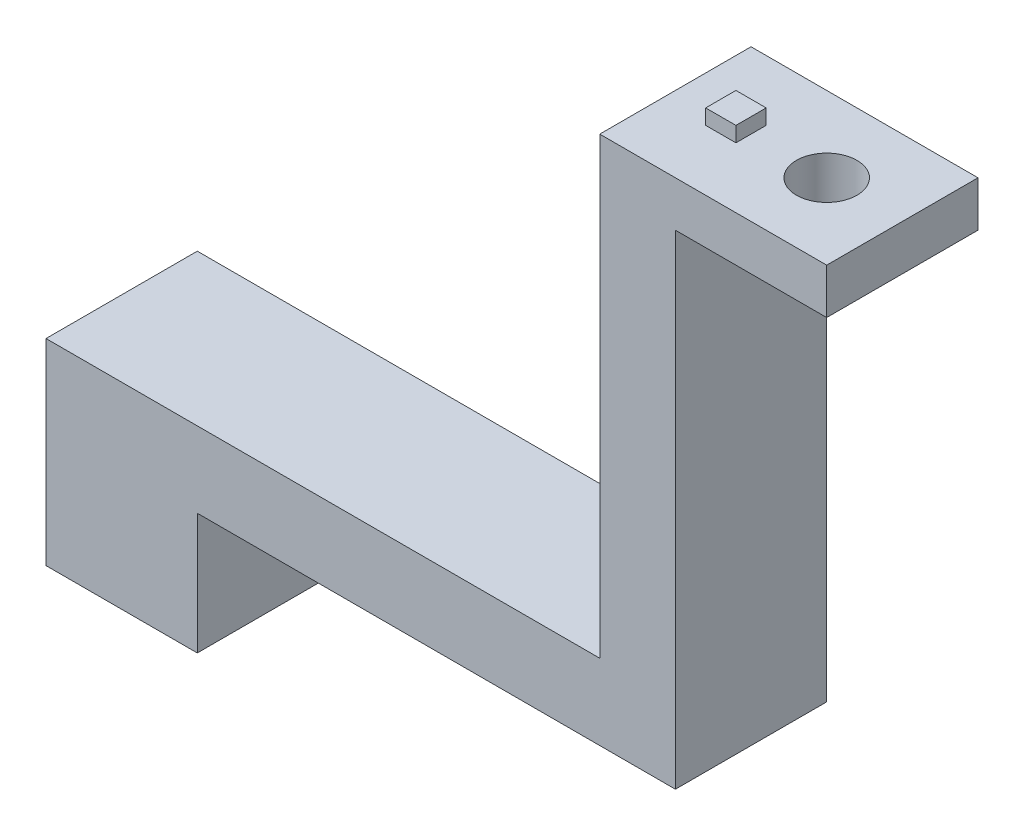
SolidWorks part; units mm, degrees
ref_plane "Front Plane" through (0, 0, 0) normal (0, 0, 1) x (1, 0, 0)
ref_plane "Top Plane" through (0, 0, 0) normal (0, 1, 0) x (1, 0, 0)
ref_plane "Right Plane" through (0, 0, 0) normal (1, 0, 0) x (0, 0, -1)
sketch "Sketch1" plane through (0, 0, 0) normal (0, 0, 1) x (1, 0, 0)
  line L0 (0, 8.6428) -> (0, -8.815) construction
  line L1 (-7.8399, 0) -> (7.1786, 0) construction
  line L2 (36.6, -2.7124) -> (36.6, 24.7717) construction
  line L3 (-5.2779, 43) -> (40.9314, 43) construction
  line L4 (10, 13) -> (36.6, 13)
  line L5 (0, 13) -> (10, 13)
  line L6 (0, 13) -> (0, 0)
  line L7 (0, 0) -> (10, 0)
  line L8 (10, 8) -> (10, 0)
  line L9 (36.6, 13) -> (36.6, 43)
  line L11 (41.6, 40) -> (41.6, 8)
  line L12 (41.6, 8) -> (10, 8)
  line L13 (41.6, 40) -> (51.6, 40)
  line L14 (51.6, 40) -> (51.6, 43)
  line L16 (36.6, 43) -> (51.6, 43)
  dimension "D4" = 30
  dimension "D1" = 36.6
  dimension "D2" = 10
  dimension "D3" = 13
  dimension "D5" = 15
  dimension "D6" = 5
  dimension "D7" = 5
  dimension "D8" = 3
  dimension "D9" = 8
extrude "Boss-Extrude1" add sketch "Sketch1" along normal blind 10
sketch "Sketch2" plane through (0, 0, 0) normal (0, -1, 0) x (1, 0, 0)
  line L0 (5, 15.6268) -> (5, -4.9051) construction
  line L1 (2.45, 6.55) -> (7.55, 6.55)
  line L2 (2.45, 6.55) -> (2.45, 3.45)
  line L3 (2.45, 3.45) -> (7.55, 3.45)
  line L4 (7.55, 6.55) -> (7.55, 3.45)
  line L5 (-4.1598, 5) -> (14.1324, 5) construction
  line L11 (0, 0) -> (10, 0) construction
  line L12 (0, 10) -> (0, 0) construction
  dimension "D1" = 5
  dimension "D2" = 5
  dimension "D3" = 5.1
  dimension "D4" = 3.1
extrude "Cut-Extrude1" cut sketch "Sketch2" against normal blind 10 contours L2 L1 L4 L3
sketch "Sketch3" plane through (0, 43, 0) normal (0, 1, 0) x (1, 0, 0)
  line L0 (29.4648, -5) -> (60.8247, -5) construction
  line L3 (51.6, 0) -> (36.6, 0) construction
  line L4 (51.6, -10) -> (51.6, 0) construction
  line L6 (39.6, -6) -> (41.6, -6)
  line L7 (39.6, -6) -> (39.6, -4)
  line L8 (39.6, -4) -> (41.6, -4)
  line L9 (41.6, -6) -> (41.6, -4)
  circle A0 centre (46.6, -5) radius 2
  dimension "D2" = 4
  dimension "D3" = 3
  dimension "D1" = 5
  dimension "D4" = 2
  dimension "D5" = 2
  dimension "D6" = 3
extrude "Boss-Extrude2" add sketch "Sketch3" along normal blind 1 contours L7 L6 L9 L8
sketch "Sketch11" plane through (0, 43, 0) normal (0, 1, 0) x (1, 0, 0)
  line L0 (29.4648, -5) -> (60.8247, -5) construction
  line L2 (51.6, -10) -> (51.6, 0) construction
  line L5 (39.6, -6) -> (41.6, -6) construction
  line L6 (39.6, -6) -> (41.6, -6)
  line L7 (39.6, -6) -> (39.6, -4)
  line L8 (39.6, -4) -> (41.6, -4)
  line L9 (41.6, -6) -> (41.6, -4)
  circle A0 centre (46.6, -5) radius 2
  dimension "D2" = 4
  dimension "D3" = 0
  dimension "D1" = 3
  dimension "D4" = 2
  dimension "D5" = 2
  dimension "D6" = 3
extrude "Cut-Extrude4" cut sketch "Sketch11" against normal up to next contours A0
